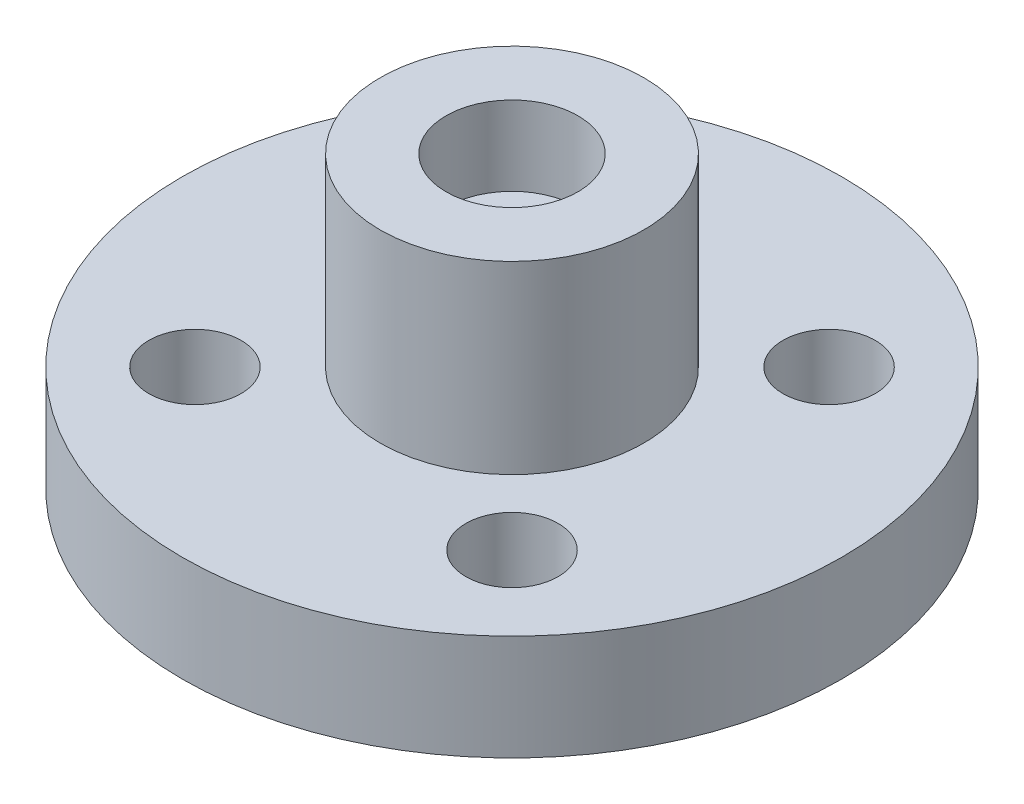
SolidWorks part; units mm, degrees
material "ABS"
ref_plane "Front Plane" through (0, 0, 0) normal (0, 0, 1) x (1, 0, 0)
ref_plane "Top Plane" through (0, 0, 0) normal (0, 1, 0) x (1, 0, 0)
ref_plane "Right Plane" through (0, 0, 0) normal (1, 0, 0) x (0, 0, -1)
sketch "Sketch1" plane through (0, 0, 0) normal (0, 1, 0) x (1, 0, 0)
  circle A0 centre (0, 0) radius 12.5
  dimension "D1" = 25
extrude "Boss-Extrude1" add sketch "Sketch1" along normal blind 4
sketch "Sketch2" plane through (0, 4, 0) normal (0, 1, 0) x (1, 0, 0)
  circle A0 centre (0, 0) radius 2.5
  circle A1 centre (0, 0) radius 5
  dimension "D1" = 5
  dimension "D2" = 10
extrude "Boss-Extrude2" add sketch "Sketch2" along normal blind 7
sketch "Sketch3" plane through (0, 4, 0) normal (0, 1, 0) x (1, 0, 0)
  line L0 (-8.355, 0) -> (0, 0) construction
  line L1 (0, 0) -> (-6.0104, 6.0104) construction
  line L2 (0, 0) -> (6.0104, 6.0104) construction
  line L3 (0, 0) -> (6.0104, -6.0104) construction
  line L4 (0, 0) -> (-6.0104, -6.0104) construction
  circle A0 centre (-6.0104, 6.0104) radius 1.75
  circle A1 centre (6.0104, 6.0104) radius 1.75
  circle A2 centre (6.0104, -6.0104) radius 1.75
  circle A3 centre (-6.0104, -6.0104) radius 1.75
  point P13 (0, 0)
  dimension "D2" = 3.5
  dimension "D1" = 45
  dimension "D3" = 8.5
  dimension "D4" = 4
extrude "Cut-Extrude1" cut sketch "Sketch3" against normal up to next
extrude "Boss-Extrude3" add sketch "Sketch2<2>" along normal blind 4 contours A0 region at (0, 4, 0)
sketch "Sketch2<2>" plane through (0, 4, 0) normal (0, 1, 0) x (1, 0, 0) same geometry as "Sketch2"
